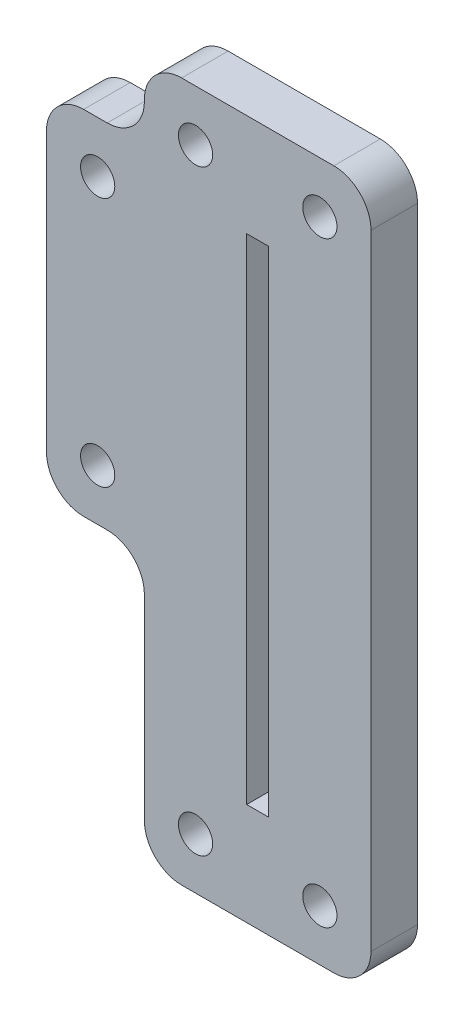
SolidWorks part; units mm, degrees
ref_plane "Front Plane" through (0, 0, 0) normal (0, 0, 1) x (1, 0, 0)
ref_plane "Top Plane" through (0, 0, 0) normal (0, 1, 0) x (1, 0, 0)
ref_plane "Right Plane" through (0, 0, 0) normal (1, 0, 0) x (0, 0, -1)
sketch "Sketch1" plane through (0, 0, 0) normal (0, 0, 1) x (1, 0, 0)
  line L0 (-31.4532, -3.5825) -> (-31.4532, -46.2225)
  line L1 (-44.3832, -1.0425) -> (-33.9932, -1.0425)
  line L2 (-53.6057, -8.7842) -> (-53.6057, -27.7707)
  line L3 (-44.3832, -48.7625) -> (-33.9932, -48.7625)
  line L5 (-39.9382, -8.0275) -> (-38.4382, -8.0275)
  line L6 (-39.9382, -8.0275) -> (-39.9382, -41.7775)
  line L7 (-39.9382, -41.7775) -> (-38.4382, -41.7775)
  line L8 (-38.4382, -8.0275) -> (-38.4382, -41.7775)
  line L9 (-51.0657, -6.2442) -> (-49.4632, -6.2442)
  line L10 (-46.9232, -3.5825) -> (-46.9232, -3.7042)
  line L11 (-46.9232, -46.2225) -> (-46.9232, -32.8507)
  line L13 (-49.4632, -30.3107) -> (-51.0657, -30.3107)
  circle A0 centre (-43.4307, -4.535) radius 1.1684
  circle A1 centre (-34.9457, -4.535) radius 1.1684
  circle A2 centre (-43.4307, -45.27) radius 1.1684
  circle A3 centre (-34.9457, -45.27) radius 1.1684
  arc A4 (-31.4532, -3.5825) -> (-33.9932, -1.0425) centre (-33.9932, -3.5825) ccw
  arc A5 (-44.3832, -1.0425) -> (-46.9232, -3.5825) centre (-44.3832, -3.5825) ccw
  arc A6 (-31.4532, -46.2225) -> (-33.9932, -48.7625) centre (-33.9932, -46.2225) cw
  arc A7 (-46.9232, -46.2225) -> (-44.3832, -48.7625) centre (-44.3832, -46.2225) ccw
  circle A8 centre (-50.1132, -9.7367) radius 1.1684
  circle A9 centre (-50.1132, -26.8182) radius 1.1684
  arc A10 (-46.9232, -32.8507) -> (-49.4632, -30.3107) centre (-49.4632, -32.8507) ccw
  arc A11 (-53.6057, -27.7707) -> (-51.0657, -30.3107) centre (-51.0657, -27.7707) ccw
  arc A12 (-46.9232, -3.7042) -> (-49.4632, -6.2442) centre (-49.4632, -3.7042) cw
  arc A13 (-53.6057, -8.7842) -> (-51.0657, -6.2442) centre (-51.0657, -8.7842) cw
  dimension "D7" = 2.3368
  dimension "D8" = 2.3368
  dimension "D9" = 2.3368
  dimension "D10" = 2.3368
  dimension "D11" = 3.4925
  dimension "D12" = 17.0815
  dimension "D13" = 3.4925
  dimension "D14" = 3.4925
  dimension "D15" = 3.4925
  dimension "D16" = 3.4925
  dimension "D17" = 3.4925
  dimension "D18" = 1.7093
  dimension "D19" = 2.54
  dimension "D23" = 2.54
  dimension "D24" = 10.175
  dimension "D21" = 10.175
  dimension "D25" = 3.4925
  dimension "D2" = 6.985
  dimension "D3" = 33.75
  dimension "D4" = 6.985
  dimension "D5" = 1.5
  dimension "D6" = 6.985
  dimension "D20" = 3.4925
  dimension "D22" = 3.4925
extrude "Boss-Extrude1" add sketch "Sketch1" along normal blind 3.175
